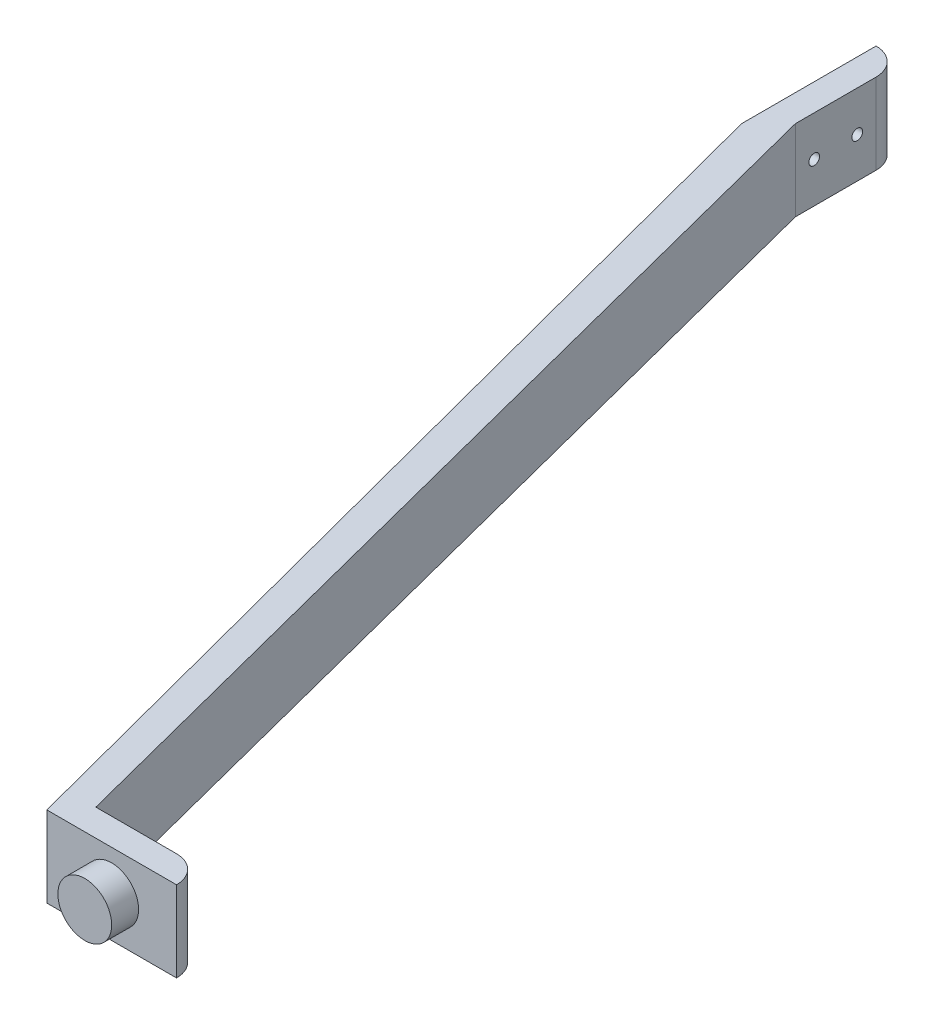
SolidWorks part; units mm, degrees
ref_plane "Plan de face" through (0, 0, 0) normal (0, 0, 1) x (1, 0, 0)
ref_plane "Plan de dessus" through (0, 0, 0) normal (0, 1, 0) x (1, 0, 0)
ref_plane "Plan de droite" through (0, 0, 0) normal (1, 0, 0) x (0, 0, -1)
sketch "Esquisse1" plane through (0, 0, 0) normal (0, 1, 0) x (1, 0, 0)
  line L1 (70, 200) -> (-70, 200)
  line L2 (70, 200) -> (70, -200)
  line L3 (70, -200) -> (-70, -200)
  line L4 (-70, 200) -> (-70, -200)
  line L5 (70, 200) -> (-70, -200) construction
  line L6 (70, -200) -> (-70, 200) construction
  point P0 (0, 0)
extrude "Boss.-Extru.1" add sketch "Esquisse1" along normal blind 30
sketch "Esquisse2" plane through (0, 30, 0) normal (0, 1, 0) x (1, 0, 0)
  line L0 (-70, 200) -> (-60, 200)
  line L1 (70, 200) -> (-70, 200) construction
  line L2 (-60, 200) -> (-60, 160)
  line L3 (70, -200) -> (31.7864, -200)
  line L4 (-70, -200) -> (70, -200) construction
  line L5 (70, -200) -> (70, -190)
  line L6 (70, -200) -> (70, 200) construction
  line L7 (70, -190) -> (30, -190)
  line L8 (-60, 160) -> (30, -190)
  line L9 (31.7864, -200) -> (21.7864, -200)
  line L10 (-70, 200) -> (-70, 150)
  line L11 (-70, 200) -> (-70, -200) construction
  line L12 (-70, 150) -> (21.7864, -200)
  line L13 (-70, 200) -> (-60, 200)
  line M10 (-70, 200) -> (-70, -200)
  line M11 (-70, -200) -> (70, -200)
  line M12 (70, -200) -> (70, 200)
  line M13 (70, 200) -> (-70, 200)
extrude "Enlèv. mat.-Extru.2" cut sketch "Esquisse2" against normal blind 30 contours L12 M10 M11 | L2 L8 L7 M12 M13 region at (20.7725, 30, -40.3004) region at (-39.4045, 30, 83.3333)
sketch "Esquisse3" plane through (-70, 0, 0) normal (-1, 0, 0) x (0, 0, 1)
  line L0 (-200, 30) -> (-150, 0)
  line L1 (-150, 30) -> (-200, 0)
  line L4 (-175, 15) -> (-183, 15)
  line L5 (-175, 15) -> (-167, 15)
  circle A0 centre (-183, 15) radius 2
  circle A1 centre (-167, 15) radius 2
extrude "Enlèv. mat.-Extru.3" cut sketch "Esquisse3" against normal through all contours A0 | A1 region at (-70, 15, -184.9434) region at (-70, 16.9434, -167)
sketch "Esquisse4" plane through (0, 0, 200) normal (0, 0, 1) x (1, 0, 0)
  line L0 (21.7864, 30) -> (70, 0)
  line L1 (21.7864, 0) -> (70, 0) construction
  circle A0 centre (45.8932, 15) radius 10
extrude "Boss.-Extru.3" add sketch "Esquisse4" along normal blind 10 contours L0 A0 | L0 A0 region at (48.1354, 18.6035, 200) region at (43.651, 11.3965, 200)
fillet "Congé1" radius 10 1 edges at (-60, 15, -200)
fillet "Congé2" radius 10 1 edges at (70, 15, 190)
